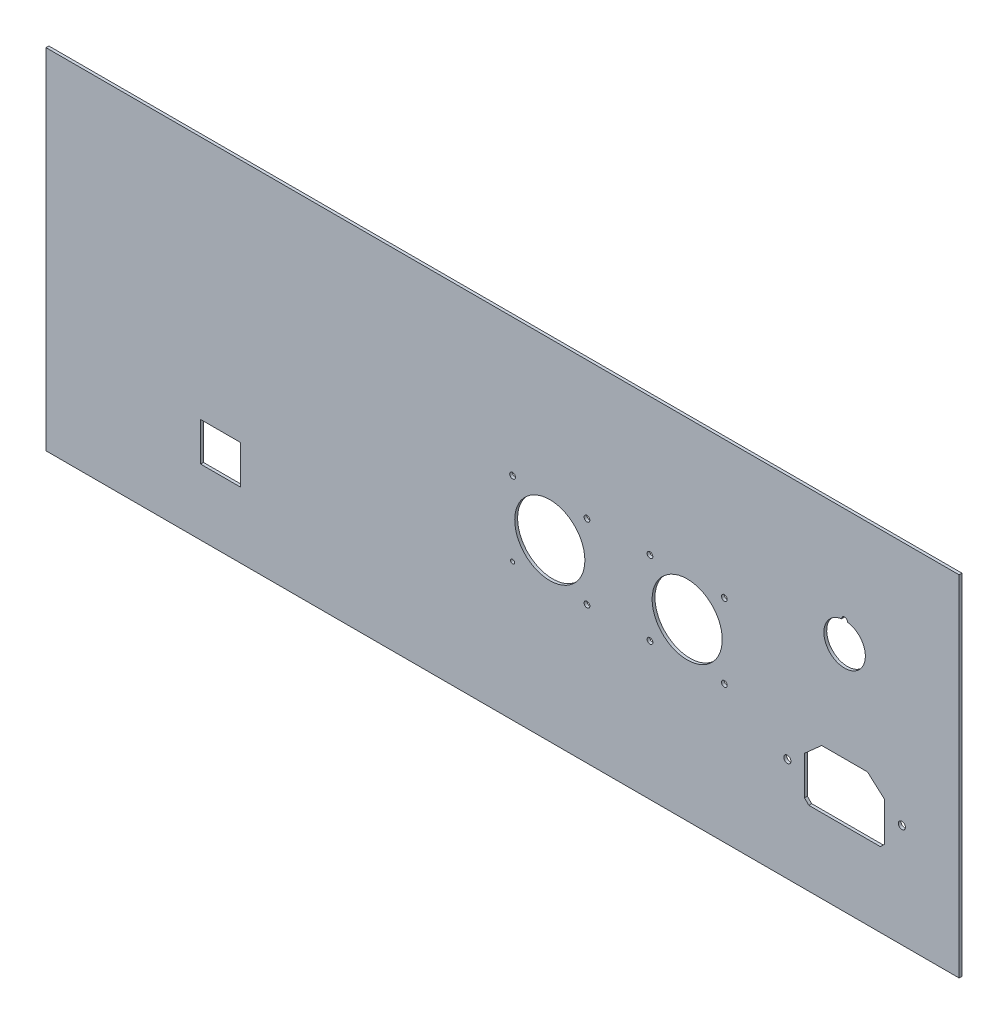
SolidWorks part; units mm, degrees
ref_plane "Спереди" through (0, 0, 0) normal (0, 0, 1) x (1, 0, 0)
ref_plane "Сверху" through (0, 0, 0) normal (0, 1, 0) x (1, 0, 0)
ref_plane "Справа" through (0, 0, 0) normal (1, 0, 0) x (0, 0, -1)
sketch "Эскиз1" plane through (0, 0, 0) normal (0, 0, 1) x (1, 0, 0)
  line L1 (-57.7, 25.5473) -> (261.3, 25.5473)
  line L2 (-57.7, 25.5473) -> (-57.7, -96.4527)
  line L3 (-57.7, -96.4527) -> (261.3, -96.4527)
  line L4 (261.3, 25.5473) -> (261.3, -96.4527)
  dimension "D1" = 319
  dimension "D2" = 122
sheet metal parameters "Листовой металл1" thickness 1 parameters "D1"=1.1, "Толщина"=1
base flange "Базовая кромка1" sketch "Эскиз1" thickness 1 reverse thickness direction no parameters "D1"=1.1
sketch "Эскиз2" plane through (0, 0, -1) normal (0, 0, -1) x (-1, 0, 0)
  line L0 (-261.3, -35.4527) -> (57.7, -35.4527) construction
  line L1 (-261.3, -96.4527) -> (-261.3, 25.5473) construction
  line L2 (57.7, 25.5473) -> (57.7, -96.4527) construction
  line L3 (-221.3, 25.5473) -> (-221.3, -96.4527) construction
  line L4 (-261.3, 25.5473) -> (57.7, 25.5473) construction
  line L5 (-261.3, 25.5473) -> (57.7, 25.5473) construction
  line L6 (57.7, -96.4527) -> (-261.3, -96.4527) construction
  circle A0 centre (-166.3, -35.4527) radius 12.25
  circle A1 centre (-118.3, -35.4527) radius 12.25
  arc A2 (-222.2977, -8.2716) -> (-220.3024, -8.2716) centre (-221.3, -15.4527) ccw
  arc A3 (-220.3024, -8.2716) -> (-222.2977, -8.2716) centre (-221.3, -8.2027) ccw
  dimension "D2" = 48
  dimension "D3" = 24.5
  dimension "D4" = 24.5
  dimension "D5" = 55
  dimension "D6" = 14.5
  dimension "D7" = 41
  dimension "D8" = 2
  dimension "D1" = 40
extrude "Вырез-Вытянуть1" cut sketch "Эскиз2" against normal blind 10 normal cut yes
sketch "Эскиз3" plane through (0, 0, -1) normal (0, 0, -1) x (-1, 0, 0)
  circle A0 centre (-179.3, -22.4527) radius 1
  circle A1 centre (-153.3, -22.4527) radius 1
  circle A2 centre (-179.3, -48.4527) radius 1
  circle A3 centre (-153.3, -48.4527) radius 1
  circle A4 centre (-131.3, -48.4527) radius 1
  circle A5 centre (-105.3, -48.4527) radius 0.7071
  circle A6 centre (-131.3, -22.4527) radius 1
  circle A7 centre (-105.3, -22.4527) radius 1
  dimension "D1" = 2
  dimension "D2" = 2
  dimension "D3" = 2
  dimension "D4" = 1.4142
  dimension "D5" = 2
  dimension "D6" = 2
  dimension "D7" = 2
  dimension "D8" = 2
extrude "Вырез-Вытянуть2" cut sketch "Эскиз3" against normal blind 10 normal cut yes
sketch "Эскиз4" plane through (0, 0, -1) normal (0, 0, -1) x (-1, 0, 0)
  line L0 (-221.3, -15.4527) -> (-221.3, -96.4527) construction
  line L1 (57.7, -96.4527) -> (-261.3, -96.4527) construction
  line L2 (-213.3, -50.1019) -> (-207.3, -55.4527)
  line L3 (-229.3, -50.1019) -> (-213.3, -50.1019)
  line L4 (-235.3, -55.4527) -> (-235.3, -70.4527)
  line L5 (-235.3, -70.4527) -> (-207.3, -70.4527)
  line L6 (-207.3, -55.4527) -> (-207.3, -70.4527)
  line L7 (-229.3, -50.1019) -> (-235.3, -55.4527)
  line L8 (-235.3, -55.4527) -> (-207.3, -55.4527) construction
  dimension "D1" = 16
  dimension "D2" = 14
  dimension "D3" = 15
  dimension "D4" = 8
  dimension "D5" = 28
  dimension "D6" = 20.3508
  dimension "D7" = 55
extrude "Вырез-Вытянуть3" cut sketch "Эскиз4" against normal blind 10 normal cut yes
sketch "Эскиз5" plane through (0, 0, -1) normal (0, 0, -1) x (-1, 0, 0)
  circle A0 centre (-241.3, -60.2752) radius 1.25
  circle A1 centre (-201.3, -60.2752) radius 1.25
  dimension "D1" = 2.5
  dimension "D2" = 2.5
extrude "Вырез-Вытянуть4" cut sketch "Эскиз5" against normal blind 10 normal cut yes
chamfer "Фаска1" distance 1.5 angle 45 2 edges at (207.3, -70.4527, -0.5) (235.3, -70.4527, -0.5)
sketch "Эскиз6" plane through (0, 0, -1) normal (0, 0, -1) x (-1, 0, 0)
  line L0 (-9.3, -60.9527) -> (2.7, -60.9527) construction
  line L1 (-10.3, -59.9527) -> (3.7, -59.9527)
  line L2 (-10.3, -59.9527) -> (-10.3, -73.4527)
  line L3 (-10.3, -73.4527) -> (3.7, -73.4527)
  line L4 (3.7, -59.9527) -> (3.7, -73.4527)
  line L5 (-9.3, -60.9527) -> (-9.3, -72.4527) construction
  line L6 (-9.3, -72.4527) -> (2.7, -72.4527) construction
  line L7 (2.7, -60.9527) -> (2.7, -72.4527) construction
  dimension "D1" = 1
  dimension "D2" = 1
  dimension "D3" = 1
  dimension "D4" = 1
extrude "Вырез-Вытянуть5" cut sketch "Эскиз6" against normal blind 10 normal cut yes
flat pattern "Развертка1" [suppressed]
sketch "Сгиб-Линии1" plane through (0, 0, 0) normal (0, 1, 0) x (1, 0, 0)
sketch3d "Граничная рамка1" [suppressed]
  line L0 (57.7, -88.4527, 0) -> (-251.3, -88.4527, 0) construction
  line L1 (57.7, 25.5473, 0) -> (-251.3, 25.5473, 0) construction
  line L2 (57.7, -88.4527, 0) -> (57.7, 25.5473, 0) construction
  line L3 (-251.3, -88.4527, 0) -> (-251.3, 25.5473, 0) construction
